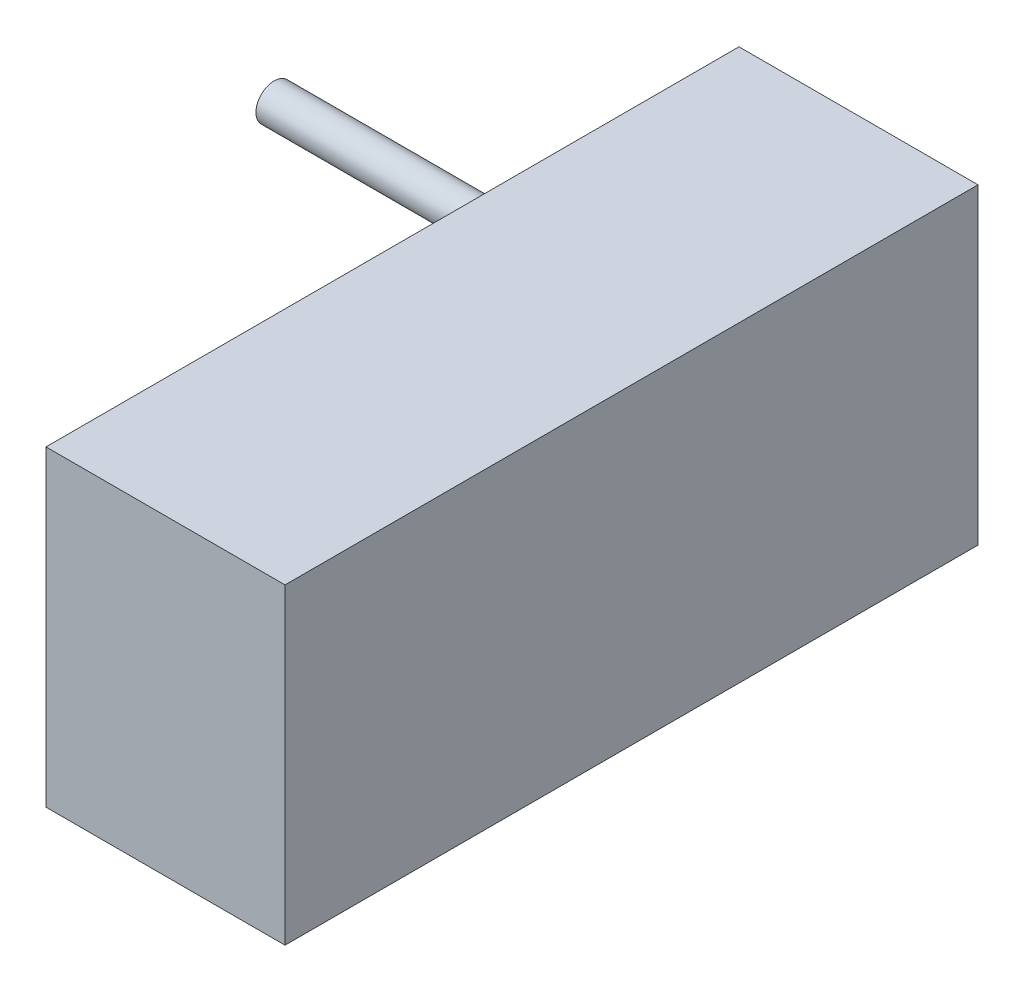
SolidWorks part; units mm, degrees
ref_plane "Plan de face" through (0, 0, 0) normal (0, 0, 1) x (1, 0, 0)
ref_plane "Plan de dessus" through (0, 0, 0) normal (0, 1, 0) x (1, 0, 0)
ref_plane "Plan de droite" through (0, 0, 0) normal (1, 0, 0) x (0, 0, -1)
sketch "Esquisse1" plane through (0, 0, 0) normal (0, 1, 0) x (1, 0, 0)
  line L0 (0, 0) -> (19.15, 0)
  line L1 (0, 0) -> (0, 55.52)
  line L2 (0, 55.52) -> (19.15, 55.52)
  line L3 (19.15, 55.52) -> (19.15, 0)
extrude "Boss.-Extru.1" add sketch "Esquisse1" along normal blind 25 contours L1 L2 L3 L0
sketch "Esquisse3" plane through (0, 0, 0) normal (1, 0, 0) x (0, 0, -1)
  circle A0 centre (45.58, 12.5) radius 1.46
  point P6 (45.4959, 12.5)
extrude "Boss.-Extru.2" add sketch "Esquisse3" against normal blind 27.3
